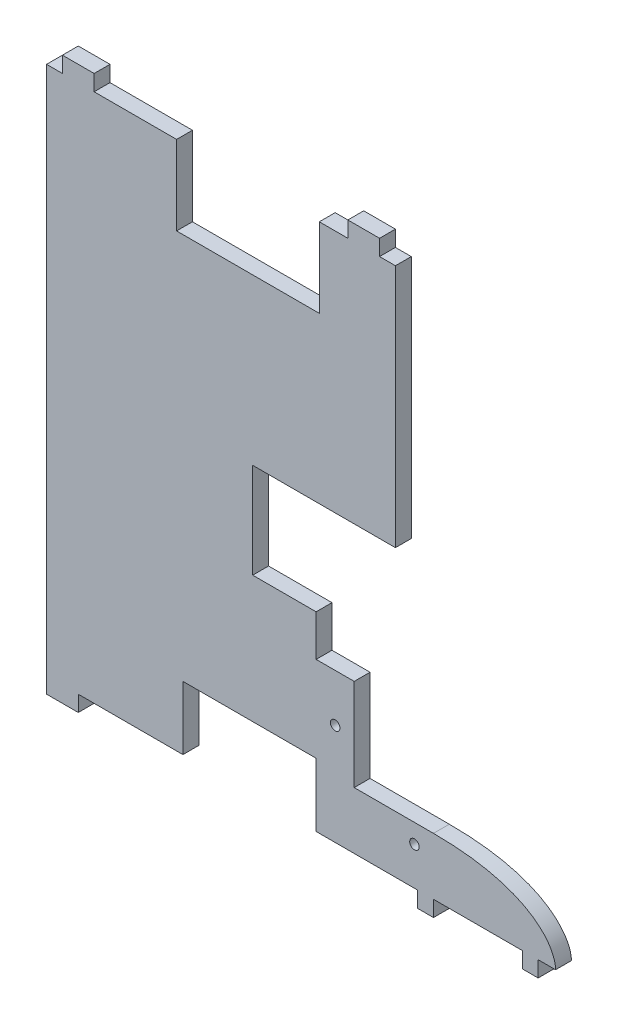
SolidWorks part; units mm, degrees
ref_plane "Plan de face" through (0, 0, 0) normal (0, 0, 1) x (1, 0, 0)
ref_plane "Plan de dessus" through (0, 0, 0) normal (0, 1, 0) x (1, 0, 0)
ref_plane "Plan de droite" through (0, 0, 0) normal (1, 0, 0) x (0, 0, -1)
sketch "Esquisse1" plane through (0, 0, 0) normal (0, 0, 1) x (1, 0, 0)
  line L1 (0, 0) -> (32, 0)
  line L2 (0, 0) -> (0, 47)
  line L3 (0, 47) -> (12, 47)
  line L4 (37, 0) -> (37, 18)
  line L6 (12, 47) -> (12, 18)
  line L7 (12, 18) -> (37, 18)
  line L8 (37, 0) -> (37, -5)
  line L9 (37, -5) -> (32, -5)
  line L10 (32, 0) -> (32, -5)
  circle A0 centre (6, 32) radius 1.5
  circle A1 centre (31, 12) radius 1.5
  dimension "D3" = 20
  dimension "D4" = 3
  dimension "D1" = 6
  dimension "D2" = 12
  dimension "D5" = 15
  dimension "D6" = 6
  dimension "D7" = 25
  dimension "D8" = 6
  dimension "D9" = 6
  dimension "D10" = 5
  dimension "D11" = 5
extrude "Boss.-Extru.1" add sketch "Esquisse1" along normal blind 5
sketch "Esquisse2" plane through (0, 0, 0) normal (0, 0, -1) x (-1, 0, 0)
  line L0 (-37, 18) -> (-12, 18) construction
  line L1 (-37, 0) -> (-65, 0)
  line L2 (-37, 0) -> (-37, 18)
  line L3 (-70, 0) -> (-75.5, 0)
  line L4 (42, 0) -> (75, 0)
  line L5 (0, 20) -> (0, 60)
  line L6 (0, 60) -> (20, 60)
  line L7 (-10, 167) -> (-1, 167)
  line L8 (0, 0) -> (-32, 0) construction
  line L9 (20, 60) -> (20, 90)
  line L10 (44, 167) -> (70, 167)
  line L11 (85, -5) -> (85, 167)
  line L12 (85, -5) -> (75, -5)
  line L13 (75, 0) -> (75, -5)
  line L14 (80, 167) -> (85, 167)
  line L15 (-70, 0) -> (-70, -5)
  line L16 (-70, -5) -> (-65, -5)
  line L17 (-65, 0) -> (-65, -5)
  line L18 (0, 20) -> (42, 20)
  line L19 (80, 167) -> (80, 172)
  line L20 (80, 172) -> (70, 172)
  line L21 (70, 167) -> (70, 172)
  line L22 (0, 47) -> (0, 0) construction
  line L23 (-20, 167) -> (-20, 172)
  line L24 (-20, 172) -> (-10, 172)
  line L25 (-10, 167) -> (-10, 172)
  line L26 (0, 0) -> (-32, 0) construction
  line L27 (42, 20) -> (42, 0)
  line L29 (-37, -5) -> (-37, 18) construction
  line L30 (-1, 167) -> (-1, 142)
  line L31 (20, 90) -> (-25, 90)
  line L32 (-1, 142) -> (44, 142)
  line L33 (-20, 167) -> (-25, 167)
  line L34 (-25, 90) -> (-25, 167)
  line L35 (44, 167) -> (44, 142)
  spline S0 degree 3 poles (-75.5, 0) (-75.5, 5.9822) (-67.6854, 18) (-37, 18) knots 0 0 0 0 1 1 1 1
  dimension "D1" = 38.5
  dimension "D2" = 20
  dimension "D3" = 167
  dimension "D4" = 85
  dimension "D5" = 5
  dimension "D6" = 30
  dimension "D7" = 5
  dimension "D8" = 10
  dimension "D9" = 10
  dimension "D10" = 10
  dimension "D11" = 140
  dimension "D12" = 5
  dimension "D13" = 42
  dimension "D14" = 20
  dimension "D15" = 40
  dimension "D16" = 45
  dimension "D17" = 5
  dimension "D18" = 5
  dimension "D19" = 25
  dimension "D20" = 45
  dimension "D21" = 24
extrude "Boss.-Extru.2" add sketch "Esquisse2" against normal blind 5
